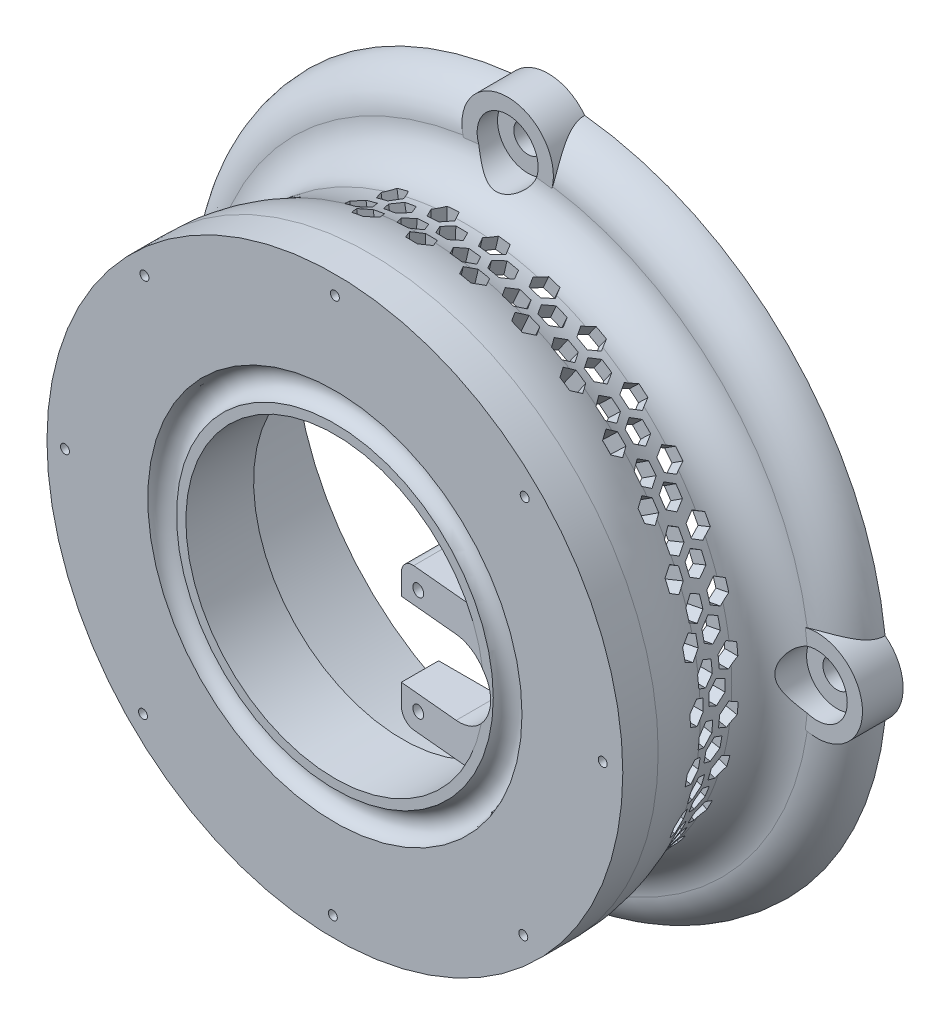
SolidWorks part; units mm, degrees
note: '?' marks a value the reader was unsure of. The reader was unsure of these and kept them because the rebuilt part matched: shared geometry of "Szkic4<2>", "Szkic25<3>".
ref_plane "Płaszczyzna przednia" through (0, 0, 0) normal (0, 0, 1) x (1, 0, 0)
ref_plane "Płaszczyzna górna" through (0, 0, 0) normal (0, 1, 0) x (1, 0, 0)
ref_plane "Płaszczyzna prawa" through (0, 0, 0) normal (1, 0, 0) x (0, 0, -1)
ref_plane "Płaszczyzna4" through (0, 0, -2) normal (0, 0, -1) x (-1, 0, 0)
sketch "Szkic2" plane through (0, 0, -2) normal (0, 0, 1) x (1, 0, 0)
  line L0 (68.9829, 1.0093) -> (-61.0171, 1.0093) construction
  circle A0 centre (3.9829, 1.0093) radius 44
  circle A1 centre (3.9829, 1.0093) radius 85
  circle A10 centre (3.9829, 1.0093) radius 65 construction
  dimension "D1" = 170
  dimension "D2" = 88
extrude "Dodanie-wyciągnięcie1" add sketch "Szkic2" against normal blind 20
ref_axis "Oś1" through (3.9829, 1.0093, -22) along (0, 0, 1)?
sketch "Szkic4" plane through (3.9829, 0, -274.858) normal (1, 0, 0) x (0, 0, -1)
  line L0 (-272.858, -79.75) -> (-272.858, 79.75) construction
  line L1 (-272.858, 56.2487) -> (-272.858, 47.7699)
  line L2 (-252.858, 1.0093) -> (-213.5294, 1.0093) construction
  line L3 (-252.858, -83.9907) -> (-252.858, 86.0093) construction
  circle A0 centre (-273.158, 52.0093) radius 4.25 construction
  arc A1 (-274.858, 55.9045) -> (-277.408, 52.0093) centre (-273.158, 52.0093) ccw construction
  arc A2 (-272.858, 56.2487) -> (-272.858, 47.7699) centre (-273.158, 52.0093) cw
revolve "Wycięcie-obrót3" cut sketch "Szkic4" angle 360 about L2
fillet "Zaokrąglenie1" [suppressed] radius 1
sketch "Szkic7" plane through (0, 0, -22) normal (0, 0, -1) x (-1, 0, 0)
  line L2 (-25, 21.5) -> (-58.093, 21.5)
  line L3 (-59.1555, -21.5) -> (-25, -21.5)
  line L4 (-58.093, 21.5) -> (-63.1555, 17)
  line L5 (-63.1555, 17) -> (-63.1555, -17)
  line L6 (-63.1555, -17) -> (-59.1555, -21.5)
  line L7 (-25, 21.5) -> (-25, -21.5)
  line L8 (0, 0) -> (-103.1393, 0) construction
  dimension "D1" = 43
  dimension "D2" = 25
extrude "Wytnij-wyciągnięcie1" cut sketch "Szkic7" against normal up to surface (6.55 mm away)
sketch "Szkic8" plane through (0, 0, 0) normal (0, 1, 0) x (1, 0, 0)
  line L0 (21.1555, 15.45) -> (21.1555, 4.45)
  line L1 (79.75, 2) -> (-79.75, 2) construction
  line L2 (-81.0171, 2) -> (88.9829, 2) construction
  line L3 (47.9713, 2) -> (47.9713, 15.45)
  line L5 (47.9713, 15.45) -> (21.1555, 15.45)
  line L6 (21.1555, 4.45) -> (47.9713, 2)
  line L8 (-40.0171, 2) -> (47.9829, 2) construction
  line L9 (42.9204, 15.45) -> (58.093, 15.45) construction
  dimension "D1" = 11
extrude "Dodanie-wyciągnięcie2" add sketch "Szkic8" along normal up to vertex and the other way up to vertex
revolve "Wycięcie-obrót4" cut sketch "Szkic4<2>" angle 360 about L2
sketch "Szkic4<2>" plane through (3.9829, 0, -274.858) normal (1, 0, 0) x (0, 0, -1) same geometry as "Szkic4"
fillet "Zaokrąglenie2" radius 4 2 edges at (21.1555, -21, -9.95) (21.1555, 21, -9.95)
sketch "Szkic11" plane through (0, 0, -22) normal (0, 0, -1) x (-1, 0, 0)
  circle A0 centre (-26.6555, 15.5) radius 1.75
  circle A3 centre (-26.6555, -15.5) radius 1.75
  dimension "D2" = 3.5
extrude "Wytnij-wyciągnięcie3" cut sketch "Szkic11" against normal through all
ref_axis "Oś2" through (3.9829, 1.0093, -22) along (0, 0, 1)?
ref_plane "Płaszczyzna5" through (3.9829, 0, 0) normal (1, 0, 0) x (0, 0, -1)
sketch "Szkic12" plane through (0, 0, -15.45) normal (0, 0, -1) x (-1, 0, 0)
  line L0 (-21.1555, 0) -> (-93.814, 0) construction
  line L1 (-21.1555, 17) -> (-21.1555, -17) construction
  line L2 (-21.1555, 11) -> (-38.9713, 11)
  line L3 (-21.1555, -11) -> (-38.9713, -11)
  line L4 (-21.1555, 11) -> (-21.1555, -11)
  arc A0 (-38.9713, 11) -> (-38.9713, -11) centre (-38.9713, 0) ccw
  dimension "D1" = 11
extrude "Wytnij-wyciągnięcie5" cut sketch "Szkic12" against normal through all
sketch "Szkic14" plane through (3.9829, 0, 0) normal (1, 0, 0) x (0, -1, 0)
  line L0 (-86.0093, 65) -> (-101.0093, 65)
  line L3 (-76.0093, 65) -> (-76.0093, 22)
  line L4 (83.9907, 22) -> (-86.0093, 22) construction
  line L5 (-76.0093, 22) -> (-86.0093, 22)
  line L6 (-86.0093, 65) -> (-76.0093, 65)
  line L8 (-1.0093, 22) -> (-1.0093, 150.2806) construction
  arc A0 (-86.0093, 22) -> (-86.0093, 65) centre (-119.7398, 43.5) ccw construction
  arc A1 (-101.0093, 65) -> (-90.3789, 53.0784) centre (-89.0093, 65) ccw
  arc A2 (-90.3789, 53.0784) -> (-79.8685, 40.294) centre (-91.738, 41.2484) cw
  arc A3 (-79.8685, 40.294) -> (-86.0093, 22) centre (-119.7398, 43.5) cw
  point P1 (-91.1471, 45.0003)
  point P16 (-84.5062, 36.6826)
  point P17 (-84.4983, 37.0312)
  point P18 (-84.0434, 37.643)
  point P19 (0, 0)
  point P20 (-79.8685, 40.294)
  dimension "D3" = 40
  dimension "D4" = 12
  dimension "D1" = 10
  dimension "D2" = 43
  dimension "D5" = 15
revolve "Obrót2" add sketch "Szkic14" angle 360 about L8
sketch "Szkic15" plane through (0, 0, -2) normal (0, 0, 1) x (1, 0, 0)
  line L0 (3.9829, 1.0093) -> (99.0167, 1.0093) construction
  circle A0 centre (3.9829, 80.5093) radius 1.325
  circle A1 centre (60.0211, 57.0475) radius 1.325
  circle A2 centre (83.0561, 0.8325) radius 1.325
  circle A3 centre (59.5943, -55.2057) radius 1.325
  circle A4 centre (3.3793, -78.2407) radius 1.325
  circle A5 centre (-52.6589, -54.7789) radius 1.325
  circle A6 centre (-75.6939, 1.436) radius 1.325
  circle A7 centre (-52.2321, 57.4743) radius 1.325
  point P23 (3.6811, 1.1343)
  dimension "D1" = 2.65
extrude "Wytnij-wyciągnięcie6" cut sketch "Szkic15" against normal blind 10
sketch "Szkic16" plane through (3.9829, 0, 0) normal (1, 0, 0) x (0, 0, -1)
  line L0 (0, 0) -> (122.0759, 0) construction
  line L1 (29, 38) -> (58, 38)
  line L2 (29, 38) -> (29, -38)
  line L3 (29, -38) -> (58, -38)
  line L4 (58, 38) -> (58, -38)
  line L7 (65, -73.9907) -> (65, 76.0093) construction
  line L8 (22, 86.0093) -> (22, -83.9907) construction
  dimension "D1" = 76
  dimension "D2" = 29
  dimension "D3" = 7
  dimension "D4" = 7
extrude "Wytnij-wyciągnięcie7" [suppressed] cut sketch "Szkic16" against normal through all
sketch "Szkic17" plane through (0, 0, -65) normal (0, 0, -1) x (-1, 0, 0)
  circle A8 centre (-3.9829, 80.2593) radius 1.325
  circle A9 centre (52.0553, 57.0475) radius 1.325
  circle A11 centre (52.0553, -55.0289) radius 1.325
  circle A12 centre (-3.9829, -78.2407) radius 1.325
  circle A13 centre (-60.0211, -55.0289) radius 1.325
  circle A14 centre (-83.2329, 1.0093) radius 1.325
  circle A15 centre (-60.0211, 57.0475) radius 1.325
  dimension "D1" = 2.65
extrude "Wytnij-wyciągnięcie8" [suppressed] cut sketch "Szkic17" against normal blind 20
fillet "Zaokrąglenie3" [suppressed] radius 13
ref_plane "Płaszczyzna6" through (88.9829, 0, 0) normal (1, 0, 0) x (0, 0, -1)
sketch "Szkic18" plane through (88.9829, 0, 0) normal (1, 0, 0) x (0, 0, -1)
  line L0 (65, 1.0093) -> (-68.0601, 1.0093) construction
  line L2 (82.2414, 1.0093) -> (79.2132, 7.04)
  line L3 (79.2132, 7.04) -> (72.0202, 9.3115)
  line L4 (72.0202, 9.3115) -> (70.6324, 9.3115)
  line L5 (70.6324, 9.3115) -> (59.9482, 15.6608)
  line L6 (59.9482, 15.6608) -> (56.2775, 16.8199)
  line L7 (56.2775, 16.8199) -> (48.7074, 15.4124)
  line L8 (48.7074, 15.4124) -> (33.0479, 17.6738)
  line L9 (33.0479, 17.6738) -> (40.7014, 6.3855)
  line L10 (40.7014, 6.3855) -> (39.8206, 4.503)
  line L11 (39.8206, 4.503) -> (39.8206, -2.4844)
  line L12 (40.7014, -4.367) -> (39.8206, -2.4844)
  line L13 (33.0479, -15.6553) -> (40.7014, -4.367)
  line L14 (48.7074, -13.3938) -> (33.0479, -15.6553)
  line L15 (56.2775, -14.8014) -> (48.7074, -13.3938)
  line L16 (59.9482, -13.6422) -> (56.2775, -14.8014)
  line L17 (70.6324, -7.293) -> (59.9482, -13.6422)
  line L18 (72.0202, -7.293) -> (70.6324, -7.293)
  line L19 (79.2132, -5.0215) -> (72.0202, -7.293)
  line L20 (82.2414, 1.0093) -> (79.2132, -5.0215)
  line L21 (78.8845, 1.0093) -> (77.101, 4.561)
  line L22 (77.101, 4.561) -> (71.5578, 6.3115)
  line L23 (71.5578, 6.3115) -> (69.8083, 6.3115)
  line L24 (69.8083, 6.3115) -> (58.7139, 12.9045)
  line L25 (58.7139, 12.9045) -> (56.0889, 13.7335)
  line L26 (56.0889, 13.7335) -> (48.7688, 12.3724)
  line L27 (48.7688, 12.3724) -> (39.344, 13.7335)
  line L28 (39.344, 13.7335) -> (44.1411, 6.6582)
  line L29 (44.1411, 6.6582) -> (42.8206, 3.8359)
  line L30 (42.8206, 3.8359) -> (42.8206, -1.8173)
  line L31 (44.1411, -4.6396) -> (42.8206, -1.8173)
  line L32 (39.344, -11.7149) -> (44.1411, -4.6396)
  line L33 (48.7688, -10.3538) -> (39.344, -11.7149)
  line L34 (56.0889, -11.7149) -> (48.7688, -10.3538)
  line L35 (58.7139, -10.886) -> (56.0889, -11.7149)
  line L36 (69.8083, -4.293) -> (58.7139, -10.886)
  line L37 (71.5578, -4.293) -> (69.8083, -4.293)
  line L38 (77.101, -2.5424) -> (71.5578, -4.293)
  line L39 (78.8845, 1.0093) -> (77.101, -2.5424)
  line L40 (65, -1.9907) -> (-68.0601, -1.9907)
  line L41 (65, -98.9907) -> (65, 101.0093) construction
  point P16 (39.8206, 1.0093)
  dimension "D1" = 3
extrude "Wytnij-wyciągnięcie9" [suppressed] cut sketch "Szkic18" against normal blind 6 contours L0 L2 L3 L4 L5 L6 L7 L8 L9 L10 L11 L30 L29 L28 L27 L26 L25 L24 L23 L22 L21 | L20 L40 L39 L38 L37 L36 L35 L34 L33 L32 L31 L30 L11 L12 L13 L14 L15 L16 L17 L18 L19 | L20 L0 L39 L40 | L30 L0 L11 L40
sketch "Szkic19" [suppressed] plane through (0, 0, -22) normal (0, 0, -1) x (-1, 0, 0)
  line L0 (-40.0802, 26.1683) -> (-65.9424, 43.2705)
  line L1 (-83.2329, 1.0093) -> (99.2698, 1.0093) construction
  line L2 (-40.0802, -24.1498) -> (-65.9424, -41.252)
  arc A0 (-41.7894, -21.5) -> (-42.9204, 21.5) centre (-3.9829, 1.0093) ccw construction
  arc A1 (-65.9424, 43.2705) -> (-65.9424, -41.252) centre (-3.9829, 1.0093) cw
  arc A3 (-40.0802, 26.1683) -> (-40.0802, -24.1498) centre (-3.9829, 1.0093) cw
  circle A4 centre (-3.9829, 1.0093) radius 75 construction
extrude "Wytnij-wyciągnięcie10" [suppressed] cut sketch "Szkic19" against normal blind 12
fillet "Zaokrąglenie4" [suppressed] radius 2
sketch "Szkic20" plane through (0, 0, 0) normal (1, 0, 0) x (0, 0, -1)
  line L0 (0, 0) -> (109, 0) construction
  line L1 (39.0718, 14.9113) -> (42.5359, 16.9113)
  line L2 (42.5359, 16.9113) -> (45.9536, 14.9381)
  line L3 (42.5359, 12.9649) -> (45.9536, 14.9381)
  line L4 (39.0718, 14.9113) -> (42.5359, 12.9649)
  line L5 (50.5359, 16.9113) -> (53.9536, 14.9381)
  line L7 (50.5359, 12.9649) -> (53.9536, 14.9381)
  line L8 (47.0718, 14.9113) -> (50.5359, 16.9113)
  line L9 (47.0718, 14.9113) -> (50.5359, 12.9649)
  line L10 (58.5359, 16.9113) -> (61.9536, 14.9381)
  line L11 (58.5359, 12.9649) -> (61.9536, 14.9381)
  line L12 (55.0718, 14.9113) -> (58.5359, 16.9113)
  line L13 (55.0718, 14.9113) -> (58.5359, 12.9649)
  line L14 (55.0718, -14.9113) -> (58.5359, -12.9649)
  line L15 (55.0718, -14.9113) -> (58.5359, -16.9113)
  line L16 (58.5359, -12.9649) -> (61.9536, -14.9381)
  line L17 (58.5359, -16.9113) -> (61.9536, -14.9381)
  line L18 (47.0718, -14.9113) -> (50.5359, -12.9649)
  line L19 (47.0718, -14.9113) -> (50.5359, -16.9113)
  line L20 (50.5359, -12.9649) -> (53.9536, -14.9381)
  line L21 (50.5359, -16.9113) -> (53.9536, -14.9381)
  line L22 (39.0718, -14.9113) -> (42.5359, -12.9649)
  line L23 (42.5359, -12.9649) -> (45.9536, -14.9381)
  line L24 (42.5359, -16.9113) -> (45.9536, -14.9381)
  line L25 (39.0718, -14.9113) -> (42.5359, -16.9113)
  line L26 (65, -98.9907) -> (65, 101.0093) construction
  line L30 (40, 0) -> (149, 0) construction
  line L31 (31.0718, 5) -> (34.5359, 7)
  line L32 (34.5359, 7) -> (38, 5)
  line L33 (17.5359, 3) -> (38, 5)
  line L34 (31.0718, 5) -> (17.5359, 3)
  line L35 (35.0718, 0) -> (0, 0) construction
  line L36 (17.5359, -15.38) -> (17.5359, 15.38) construction
  line L37 (39.0718, 5) -> (42.5359, 7)
  line L38 (42.5359, 7) -> (46, 5)
  line L39 (25.5359, 3) -> (46, 5)
  line L40 (39.0718, 5) -> (25.5359, 3)
  line L41 (25.5359, -15.38) -> (25.5359, 15.38) construction
  line L42 (47.0718, 5) -> (50.5359, 7)
  line L43 (50.5359, 7) -> (54, 5)
  line L44 (33.5359, 3) -> (54, 5)
  line L45 (47.0718, 5) -> (33.5359, 3)
  line L46 (33.5359, -15.38) -> (33.5359, 15.38) construction
  line L47 (55.0718, 5) -> (58.5359, 7)
  line L48 (58.5359, 7) -> (62, 5)
  line L49 (41.5359, 3) -> (62, 5)
  line L50 (55.0718, 5) -> (41.5359, 3)
  line L51 (41.5359, -15.38) -> (41.5359, 15.38) construction
  line L52 (63.0718, 5) -> (66.5359, 7)
  line L53 (66.5359, 7) -> (70, 5)
  line L54 (49.5359, 3) -> (70, 5)
  line L55 (63.0718, 5) -> (49.5359, 3)
  line L56 (49.5359, -15.38) -> (49.5359, 15.38) construction
  line L57 (30.8787, 17.2091) -> (38.5359, 21.63)
  line L58 (38.5359, 21.63) -> (58.726, 9.9732)
  line L59 (38.5359, 8) -> (58.726, 9.9732)
  line L60 (30.8787, 17.2091) -> (38.5359, 8)
  line L61 (38.8787, 17.2091) -> (46.5359, 21.63)
  line L62 (46.5359, 21.63) -> (66.726, 9.9732)
  line L63 (46.5359, 8) -> (66.726, 9.9732)
  line L64 (38.8787, 17.2091) -> (46.5359, 8)
  line L65 (46.8787, 17.2091) -> (54.5359, 21.63)
  line L66 (54.5359, 21.63) -> (74.726, 9.9732)
  line L67 (54.5359, 8) -> (74.726, 9.9732)
  line L68 (46.8787, 17.2091) -> (54.5359, 8)
  line L69 (54.8787, 17.2091) -> (62.5359, 21.63)
  line L70 (62.5359, 21.63) -> (82.726, 9.9732)
  line L71 (62.5359, 8) -> (82.726, 9.9732)
  line L72 (54.8787, 17.2091) -> (62.5359, 8)
  line L73 (54.8787, -17.2091) -> (62.5359, -8)
  line L74 (62.5359, -8) -> (82.726, -9.9732)
  line L75 (62.5359, -21.63) -> (82.726, -9.9732)
  line L76 (54.8787, -17.2091) -> (62.5359, -21.63)
  line L77 (46.8787, -17.2091) -> (54.5359, -8)
  line L78 (54.5359, -8) -> (74.726, -9.9732)
  line L79 (54.5359, -21.63) -> (74.726, -9.9732)
  line L80 (46.8787, -17.2091) -> (54.5359, -21.63)
  line L81 (38.8787, -17.2091) -> (46.5359, -8)
  line L82 (46.5359, -8) -> (66.726, -9.9732)
  line L83 (46.5359, -21.63) -> (66.726, -9.9732)
  line L84 (38.8787, -17.2091) -> (46.5359, -21.63)
  line L85 (30.8787, -17.2091) -> (38.5359, -8)
  line L86 (38.5359, -8) -> (58.726, -9.9732)
  line L87 (38.5359, -21.63) -> (58.726, -9.9732)
  line L88 (30.8787, -17.2091) -> (38.5359, -21.63)
  line L89 (63.0718, -5) -> (49.5359, -3)
  line L90 (49.5359, -3) -> (70, -5)
  line L91 (66.5359, -7) -> (70, -5)
  line L92 (63.0718, -5) -> (66.5359, -7)
  line L93 (55.0718, -5) -> (41.5359, -3)
  line L94 (41.5359, -3) -> (62, -5)
  line L95 (58.5359, -7) -> (62, -5)
  line L96 (55.0718, -5) -> (58.5359, -7)
  line L97 (47.0718, -5) -> (33.5359, -3)
  line L98 (33.5359, -3) -> (54, -5)
  line L99 (50.5359, -7) -> (54, -5)
  line L100 (47.0718, -5) -> (50.5359, -7)
  line L101 (39.0718, -5) -> (25.5359, -3)
  line L102 (25.5359, -3) -> (46, -5)
  line L103 (42.5359, -7) -> (46, -5)
  line L104 (39.0718, -5) -> (42.5359, -7)
  line L105 (31.0718, -5) -> (17.5359, -3)
  line L106 (17.5359, -3) -> (38, -5)
  line L107 (34.5359, -7) -> (38, -5)
  line L108 (31.0718, -5) -> (34.5359, -7)
  line L109 (67.0718, 0) -> (70.5359, 2)
  line L110 (70.5359, 2) -> (74, 0)
  line L111 (70.5359, -2) -> (74, 0)
  line L112 (67.0718, 0) -> (70.5359, -2)
  line L113 (59.0718, 0) -> (62.5359, 2)
  line L114 (62.5359, 2) -> (66, 0)
  line L115 (62.5359, -2) -> (66, 0)
  line L116 (59.0718, 0) -> (62.5359, -2)
  line L117 (51.0718, 0) -> (54.5359, 2)
  line L118 (54.5359, 2) -> (58, 0)
  line L119 (54.5359, -2) -> (58, 0)
  line L120 (51.0718, 0) -> (54.5359, -2)
  line L121 (43.0718, 0) -> (46.5359, 2)
  line L122 (46.5359, 2) -> (50, 0)
  line L123 (46.5359, -2) -> (50, 0)
  line L124 (43.0718, 0) -> (46.5359, -2)
  line L125 (35.0718, 0) -> (38.5359, 2)
  line L126 (38.5359, 2) -> (42, 0)
  line L127 (38.5359, -2) -> (42, 0)
  line L128 (27.0718, 0) -> (3.9914, 0.2614)
  line L129 (3.9914, 0.2614) -> (0, 0)
  line L130 (3.9914, -0.2614) -> (0, 0)
  line L131 (27.0718, 0) -> (3.9914, -0.2614)
  line L132 (35.0718, 0) -> (38.5359, -2)
  line L133 (32, 0) -> (141, 0) construction
  line L134 (24, 0) -> (133, 0) construction
  line L135 (16, 0) -> (125, 0) construction
  line L136 (8, 0) -> (117, 0) construction
  point P74 (49.5359, 0)
  point P87 (41.5359, 0)
  point P88 (33.5359, 0)
  point P89 (25.5359, 0)
  point P90 (17.5359, 0)
  dimension "D1" = 2.9916
  dimension "D2" = 4
  dimension "D3" = 65
  dimension "D4" = 3
  dimension "D6" = 3
  dimension "D8" = 3
  dimension "D5" = 6
  dimension "D7" = 5
  dimension "D9" = 4
extrude "Wytnij-wyciągnięcie11" [suppressed] cut sketch "Szkic20" along normal through all
sketch "Szkic21" plane through (0, 0, 0) normal (1, 0, 0) x (0, 0, -1)
  line L0 (22, 1.0093) -> (75, 1.0093) construction
  line L3 (40.5, 4.4734) -> (37.5, 2.7413)
  line L4 (48.5, 4.4734) -> (45.5, 2.7413)
  line L5 (45.5, 2.7413) -> (45.5, -0.7228)
  line L6 (45.5, -0.7228) -> (48.5, -2.4548)
  line L7 (48.5, -2.4548) -> (51.5, -0.7228)
  line L8 (51.5, -0.7228) -> (51.5, 2.7413)
  line L9 (51.5, 2.7413) -> (48.5, 4.4734)
  line L10 (37.5, 2.7413) -> (37.5, -0.7228)
  line L11 (37.5, -0.7228) -> (40.5, -2.4548)
  line L12 (40.5, -2.4548) -> (43.5, -0.7228)
  line L13 (43.5, -0.7228) -> (43.5, 2.7413)
  line L14 (43.5, 2.7413) -> (40.5, 4.4734)
  line L15 (14, 1.0093) -> (67, 1.0093) construction
  line L16 (32.5, 4.4734) -> (29.5, 2.7413)
  line L17 (29.5, 2.7413) -> (29.5, -0.7228)
  line L18 (29.5, -0.7228) -> (32.5, -2.4548)
  line L19 (32.5, -2.4548) -> (35.5, -0.7228)
  line L20 (35.5, -0.7228) -> (35.5, 2.7413)
  line L21 (35.5, 2.7413) -> (32.5, 4.4734)
  line L22 (6, 1.0093) -> (59, 1.0093) construction
  line L23 (40.5, 12.4734) -> (37.5, 10.7413)
  line L24 (37.5, 10.7413) -> (37.5, 7.2772)
  line L25 (37.5, 7.2772) -> (40.5, 5.5452)
  line L26 (40.5, 5.5452) -> (43.5, 7.2772)
  line L27 (43.5, 7.2772) -> (43.5, 10.7413)
  line L28 (43.5, 10.7413) -> (40.5, 12.4734)
  line L29 (14, 9.0093) -> (67, 9.0093) construction
  line L30 (32.5, 12.4734) -> (29.5, 10.7413)
  line L31 (29.5, 10.7413) -> (29.5, 7.2772)
  line L32 (29.5, 7.2772) -> (32.5, 5.5452)
  line L33 (32.5, 5.5452) -> (35.5, 7.2772)
  line L34 (35.5, 7.2772) -> (35.5, 10.7413)
  line L35 (35.5, 10.7413) -> (32.5, 12.4734)
  line L36 (6, 9.0093) -> (59, 9.0093) construction
  line L37 (40.5, 20.4734) -> (37.5, 18.7413)
  line L38 (37.5, 18.7413) -> (37.5, 15.2772)
  line L39 (37.5, 15.2772) -> (40.5, 13.5452)
  line L40 (40.5, 13.5452) -> (43.5, 15.2772)
  line L41 (43.5, 15.2772) -> (43.5, 18.7413)
  line L42 (43.5, 18.7413) -> (40.5, 20.4734)
  line L43 (14, 17.0093) -> (67, 17.0093) construction
  line L44 (32.5, 20.4734) -> (29.5, 18.7413)
  line L45 (29.5, 18.7413) -> (29.5, 15.2772)
  line L46 (29.5, 15.2772) -> (32.5, 13.5452)
  line L47 (32.5, 13.5452) -> (35.5, 15.2772)
  line L48 (35.5, 15.2772) -> (35.5, 18.7413)
  line L49 (35.5, 18.7413) -> (32.5, 20.4734)
  line L50 (6, 17.0093) -> (59, 17.0093) construction
  line L51 (40.5, 28.4734) -> (37.5, 26.7413)
  line L52 (37.5, 26.7413) -> (37.5, 23.2772)
  line L53 (37.5, 23.2772) -> (40.5, 21.5452)
  line L54 (40.5, 21.5452) -> (43.5, 23.2772)
  line L55 (43.5, 23.2772) -> (43.5, 26.7413)
  line L56 (43.5, 26.7413) -> (40.5, 28.4734)
  line L57 (14, 25.0093) -> (67, 25.0093) construction
  line L58 (32.5, 28.4734) -> (29.5, 26.7413)
  line L59 (29.5, 26.7413) -> (29.5, 23.2772)
  line L60 (29.5, 23.2772) -> (32.5, 21.5452)
  line L61 (32.5, 21.5452) -> (35.5, 23.2772)
  line L62 (35.5, 23.2772) -> (35.5, 26.7413)
  line L63 (35.5, 26.7413) -> (32.5, 28.4734)
  line L64 (6, 25.0093) -> (59, 25.0093) construction
  line L65 (48.5, 12.4734) -> (45.5, 10.7413)
  line L66 (45.5, 10.7413) -> (45.5, 7.2772)
  line L67 (45.5, 7.2772) -> (48.5, 5.5452)
  line L68 (48.5, 5.5452) -> (51.5, 7.2772)
  line L69 (51.5, 7.2772) -> (51.5, 10.7413)
  line L70 (51.5, 10.7413) -> (48.5, 12.4734)
  line L71 (22, 9.0093) -> (75, 9.0093) construction
  line L72 (48.5, 20.4734) -> (45.5, 18.7413)
  line L73 (45.5, 18.7413) -> (45.5, 15.2772)
  line L74 (45.5, 15.2772) -> (48.5, 13.5452)
  line L75 (48.5, 13.5452) -> (51.5, 15.2772)
  line L76 (51.5, 15.2772) -> (51.5, 18.7413)
  line L77 (51.5, 18.7413) -> (48.5, 20.4734)
  line L78 (22, 17.0093) -> (75, 17.0093) construction
  line L79 (48.5, 28.4734) -> (45.5, 26.7413)
  line L80 (45.5, 26.7413) -> (45.5, 23.2772)
  line L81 (45.5, 23.2772) -> (48.5, 21.5452)
  line L82 (48.5, 21.5452) -> (51.5, 23.2772)
  line L83 (51.5, 23.2772) -> (51.5, 26.7413)
  line L84 (51.5, 26.7413) -> (48.5, 28.4734)
  line L85 (22, 25.0093) -> (75, 25.0093) construction
  line L86 (22, -22.9907) -> (75, -22.9907) construction
  line L87 (22, -14.9907) -> (75, -14.9907) construction
  line L88 (22, -6.9907) -> (75, -6.9907) construction
  line L89 (14, -14.9907) -> (67, -14.9907) construction
  line L90 (6, -6.9907) -> (59, -6.9907) construction
  line L91 (14, -6.9907) -> (67, -6.9907) construction
  line L92 (51.5, -24.7228) -> (48.5, -26.4548)
  line L93 (51.5, -21.2587) -> (51.5, -24.7228)
  line L94 (48.5, -19.5266) -> (51.5, -21.2587)
  line L95 (45.5, -21.2587) -> (48.5, -19.5266)
  line L96 (45.5, -24.7228) -> (45.5, -21.2587)
  line L97 (48.5, -26.4548) -> (45.5, -24.7228)
  line L98 (51.5, -16.7228) -> (48.5, -18.4548)
  line L99 (51.5, -13.2587) -> (51.5, -16.7228)
  line L100 (48.5, -11.5266) -> (51.5, -13.2587)
  line L101 (45.5, -13.2587) -> (48.5, -11.5266)
  line L102 (45.5, -16.7228) -> (45.5, -13.2587)
  line L103 (48.5, -18.4548) -> (45.5, -16.7228)
  line L104 (51.5, -8.7228) -> (48.5, -10.4548)
  line L105 (51.5, -5.2587) -> (51.5, -8.7228)
  line L106 (48.5, -3.5266) -> (51.5, -5.2587)
  line L107 (45.5, -5.2587) -> (48.5, -3.5266)
  line L108 (45.5, -8.7228) -> (45.5, -5.2587)
  line L109 (48.5, -10.4548) -> (45.5, -8.7228)
  line L110 (43.5, -16.7228) -> (40.5, -18.4548)
  line L111 (43.5, -13.2587) -> (43.5, -16.7228)
  line L112 (40.5, -11.5266) -> (43.5, -13.2587)
  line L113 (37.5, -13.2587) -> (40.5, -11.5266)
  line L114 (37.5, -16.7228) -> (37.5, -13.2587)
  line L115 (40.5, -18.4548) -> (37.5, -16.7228)
  line L116 (35.5, -8.7228) -> (32.5, -10.4548)
  line L117 (35.5, -5.2587) -> (35.5, -8.7228)
  line L118 (32.5, -3.5266) -> (35.5, -5.2587)
  line L119 (29.5, -5.2587) -> (32.5, -3.5266)
  line L120 (29.5, -8.7228) -> (29.5, -5.2587)
  line L121 (32.5, -10.4548) -> (29.5, -8.7228)
  line L122 (43.5, -8.7228) -> (40.5, -10.4548)
  line L123 (43.5, -5.2587) -> (43.5, -8.7228)
  line L124 (40.5, -3.5266) -> (43.5, -5.2587)
  line L125 (37.5, -5.2587) -> (40.5, -3.5266)
  line L126 (37.5, -8.7228) -> (37.5, -5.2587)
  line L127 (40.5, -10.4548) -> (37.5, -8.7228)
  line L128 (35.5, -0.7228) -> (32.5, -2.4548)
  line L129 (32.5, 4.4734) -> (35.5, 2.7413)
  line L130 (29.5, 2.7413) -> (32.5, 4.4734)
  line L131 (32.5, -2.4548) -> (29.5, -0.7228)
  line L132 (43.5, -0.7228) -> (40.5, -2.4548)
  line L133 (40.5, 4.4734) -> (43.5, 2.7413)
  line L134 (37.5, 2.7413) -> (40.5, 4.4734)
  line L135 (51.5, -0.7228) -> (48.5, -2.4548)
  line L136 (48.5, 4.4734) -> (51.5, 2.7413)
  line L137 (45.5, 2.7413) -> (48.5, 4.4734)
  line L138 (48.5, -2.4548) -> (45.5, -0.7228)
  line L139 (40.5, -2.4548) -> (37.5, -0.7228)
  line L140 (48.5, 1.0093) -> (48.5, -84.9338) construction
  line L141 (83, -6.9907) -> (30, -6.9907) construction
  line L142 (91, -6.9907) -> (38, -6.9907) construction
  line L143 (83, -14.9907) -> (30, -14.9907) construction
  line L144 (83, 17.0093) -> (30, 17.0093) construction
  line L145 (91, 9.0093) -> (38, 9.0093) construction
  line L146 (83, 9.0093) -> (30, 9.0093) construction
  line L147 (91, 1.0093) -> (38, 1.0093) construction
  line L148 (83, 1.0093) -> (30, 1.0093) construction
  line L149 (56.5, -2.4548) -> (59.5, -0.7228)
  line L150 (48.5, -2.4548) -> (51.5, -0.7228)
  line L151 (51.5, 2.7413) -> (48.5, 4.4734)
  line L152 (48.5, 4.4734) -> (45.5, 2.7413)
  line L153 (45.5, -0.7228) -> (48.5, -2.4548)
  line L154 (59.5, 2.7413) -> (56.5, 4.4734)
  line L155 (56.5, 4.4734) -> (53.5, 2.7413)
  line L156 (53.5, -0.7228) -> (56.5, -2.4548)
  line L157 (64.5, -2.4548) -> (67.5, -0.7228)
  line L158 (67.5, 2.7413) -> (64.5, 4.4734)
  line L159 (64.5, 4.4734) -> (61.5, 2.7413)
  line L160 (61.5, -0.7228) -> (64.5, -2.4548)
  line L161 (56.5, -10.4548) -> (59.5, -8.7228)
  line L162 (59.5, -8.7228) -> (59.5, -5.2587)
  line L163 (59.5, -5.2587) -> (56.5, -3.5266)
  line L164 (56.5, -3.5266) -> (53.5, -5.2587)
  line L165 (53.5, -5.2587) -> (53.5, -8.7228)
  line L166 (53.5, -8.7228) -> (56.5, -10.4548)
  line L167 (64.5, -10.4548) -> (67.5, -8.7228)
  line L168 (67.5, -8.7228) -> (67.5, -5.2587)
  line L169 (67.5, -5.2587) -> (64.5, -3.5266)
  line L170 (64.5, -3.5266) -> (61.5, -5.2587)
  line L171 (61.5, -5.2587) -> (61.5, -8.7228)
  line L172 (61.5, -8.7228) -> (64.5, -10.4548)
  line L173 (56.5, -18.4548) -> (59.5, -16.7228)
  line L174 (59.5, -16.7228) -> (59.5, -13.2587)
  line L175 (59.5, -13.2587) -> (56.5, -11.5266)
  line L176 (56.5, -11.5266) -> (53.5, -13.2587)
  line L177 (53.5, -13.2587) -> (53.5, -16.7228)
  line L178 (53.5, -16.7228) -> (56.5, -18.4548)
  line L179 (48.5, -10.4548) -> (51.5, -8.7228)
  line L180 (51.5, -8.7228) -> (51.5, -5.2587)
  line L181 (51.5, -5.2587) -> (48.5, -3.5266)
  line L182 (48.5, -3.5266) -> (45.5, -5.2587)
  line L183 (45.5, -5.2587) -> (45.5, -8.7228)
  line L184 (45.5, -8.7228) -> (48.5, -10.4548)
  line L185 (48.5, -18.4548) -> (51.5, -16.7228)
  line L186 (51.5, -16.7228) -> (51.5, -13.2587)
  line L187 (51.5, -13.2587) -> (48.5, -11.5266)
  line L188 (48.5, -11.5266) -> (45.5, -13.2587)
  line L189 (45.5, -13.2587) -> (45.5, -16.7228)
  line L190 (45.5, -16.7228) -> (48.5, -18.4548)
  line L191 (48.5, -26.4548) -> (51.5, -24.7228)
  line L192 (51.5, -24.7228) -> (51.5, -21.2587)
  line L193 (51.5, -21.2587) -> (48.5, -19.5266)
  line L194 (48.5, -19.5266) -> (45.5, -21.2587)
  line L195 (45.5, -21.2587) -> (45.5, -24.7228)
  line L196 (45.5, -24.7228) -> (48.5, -26.4548)
  line L197 (45.5, 26.7413) -> (48.5, 28.4734)
  line L198 (45.5, 23.2772) -> (45.5, 26.7413)
  line L199 (48.5, 21.5452) -> (45.5, 23.2772)
  line L200 (51.5, 23.2772) -> (48.5, 21.5452)
  line L201 (51.5, 26.7413) -> (51.5, 23.2772)
  line L202 (48.5, 28.4734) -> (51.5, 26.7413)
  line L203 (45.5, 18.7413) -> (48.5, 20.4734)
  line L204 (45.5, 15.2772) -> (45.5, 18.7413)
  line L205 (48.5, 13.5452) -> (45.5, 15.2772)
  line L206 (51.5, 15.2772) -> (48.5, 13.5452)
  line L207 (51.5, 18.7413) -> (51.5, 15.2772)
  line L208 (48.5, 20.4734) -> (51.5, 18.7413)
  line L209 (45.5, 10.7413) -> (48.5, 12.4734)
  line L210 (45.5, 7.2772) -> (45.5, 10.7413)
  line L211 (48.5, 5.5452) -> (45.5, 7.2772)
  line L212 (51.5, 7.2772) -> (48.5, 5.5452)
  line L213 (51.5, 10.7413) -> (51.5, 7.2772)
  line L214 (48.5, 12.4734) -> (51.5, 10.7413)
  line L215 (53.5, 18.7413) -> (56.5, 20.4734)
  line L216 (53.5, 15.2772) -> (53.5, 18.7413)
  line L217 (56.5, 13.5452) -> (53.5, 15.2772)
  line L218 (59.5, 15.2772) -> (56.5, 13.5452)
  line L219 (59.5, 18.7413) -> (59.5, 15.2772)
  line L220 (56.5, 20.4734) -> (59.5, 18.7413)
  line L221 (61.5, 10.7413) -> (64.5, 12.4734)
  line L222 (61.5, 7.2772) -> (61.5, 10.7413)
  line L223 (64.5, 5.5452) -> (61.5, 7.2772)
  line L224 (67.5, 7.2772) -> (64.5, 5.5452)
  line L225 (67.5, 10.7413) -> (67.5, 7.2772)
  line L226 (64.5, 12.4734) -> (67.5, 10.7413)
  line L227 (53.5, 10.7413) -> (56.5, 12.4734)
  line L228 (53.5, 7.2772) -> (53.5, 10.7413)
  line L229 (56.5, 5.5452) -> (53.5, 7.2772)
  line L230 (59.5, 7.2772) -> (56.5, 5.5452)
  line L231 (59.5, 10.7413) -> (59.5, 7.2772)
  line L232 (56.5, 12.4734) -> (59.5, 10.7413)
  line L233 (61.5, 2.7413) -> (64.5, 4.4734)
  line L234 (61.5, -0.7228) -> (61.5, 2.7413)
  line L235 (64.5, -2.4548) -> (61.5, -0.7228)
  line L236 (67.5, -0.7228) -> (64.5, -2.4548)
  line L237 (67.5, 2.7413) -> (67.5, -0.7228)
  line L238 (64.5, 4.4734) -> (67.5, 2.7413)
  line L239 (53.5, 2.7413) -> (56.5, 4.4734)
  line L240 (53.5, -0.7228) -> (53.5, 2.7413)
  line L241 (56.5, -2.4548) -> (53.5, -0.7228)
  line L242 (59.5, -0.7228) -> (56.5, -2.4548)
  line L243 (59.5, 2.7413) -> (59.5, -0.7228)
  line L244 (45.5, 2.7413) -> (48.5, 4.4734)
  line L245 (45.5, -0.7228) -> (45.5, 2.7413)
  line L246 (48.5, -2.4548) -> (45.5, -0.7228)
  line L247 (51.5, -0.7228) -> (48.5, -2.4548)
  line L248 (51.5, 2.7413) -> (51.5, -0.7228)
  line L249 (48.5, 4.4734) -> (51.5, 2.7413)
  line L250 (56.5, 4.4734) -> (59.5, 2.7413)
  circle A0 centre (48.5, 1.0093) radius 3 construction
  circle A1 centre (40.5, 1.0093) radius 3 construction
  circle A2 centre (32.5, 1.0093) radius 3 construction
  circle A3 centre (40.5, 9.0093) radius 3 construction
  circle A4 centre (32.5, 9.0093) radius 3 construction
  circle A5 centre (40.5, 17.0093) radius 3 construction
  circle A6 centre (32.5, 17.0093) radius 3 construction
  circle A7 centre (40.5, 25.0093) radius 3 construction
  circle A8 centre (32.5, 25.0093) radius 3 construction
  circle A9 centre (48.5, 9.0093) radius 3 construction
  circle A10 centre (48.5, 17.0093) radius 3 construction
  circle A11 centre (48.5, 25.0093) radius 3 construction
  circle A12 centre (48.5, -22.9907) radius 3 construction
  circle A13 centre (48.5, -14.9907) radius 3 construction
  circle A14 centre (48.5, -6.9907) radius 3 construction
  circle A15 centre (40.5, -14.9907) radius 3 construction
  circle A16 centre (32.5, -6.9907) radius 3 construction
  circle A17 centre (40.5, -6.9907) radius 3 construction
  circle A18 centre (56.5, -6.9907) radius 3 construction
  circle A19 centre (64.5, -6.9907) radius 3 construction
  circle A20 centre (56.5, -14.9907) radius 3 construction
  circle A21 centre (56.5, 17.0093) radius 3 construction
  circle A22 centre (64.5, 9.0093) radius 3 construction
  circle A23 centre (56.5, 9.0093) radius 3 construction
  circle A24 centre (64.5, 1.0093) radius 3 construction
  circle A25 centre (56.5, 1.0093) radius 3 construction
  dimension "D1" = 6
  dimension "D2" = 3
  dimension "D3" = 4
extrude "Wytnij-wyciągnięcie13" [suppressed] cut sketch "Szkic21" along normal through all contours L34 L35 L30 L31 L32 L33 | L20 L21 L16 L17 L18 L19 | L121 L116 L117 L118 L119 L120 | L41 L42 L37 L38 L39 L40 | L27 L28 L23 L24 L25 L26 | L13 L14 L3 L10 L11 L12 | L127 L122 L123 L124 L125 L126 | L115 L110 L111 L112 L113 L114 | L83 L84 L79 L80 L81 L82 | L76 L77 L72 L73 L74 L75 | L69 L70 L65 L66 L67 L68 | L8 L9 L4 L5 L6 L7 | L109 L104 L105 L106 L107 L108 | L103 L98 L99 L100 L101 L102 | L97 L92 L93 L94 L95 L96 | L220 L215 L216 L217 L218 L219 | L232 L227 L228 L229 L230 L231 | L243 L154 L155 L240 L156 L149 | L165 L166 L161 L162 L163 L164 | L177 L178 L173 L174 L175 L176 | L226 L221 L222 L223 L224 L225 | L237 L158 L159 L234 L160 L157 | L171 L172 L167 L168 L169 L170
sketch "Szkic22" plane through (0, 0, 0) normal (1, 0, 0) x (0, 0, -1)
  line L0 (39.3554, -34.3052) -> (39.3554, 52.6948) construction
  line L3 (32.0591, 4.1198) -> (32.0591, 0.6557)
  line L4 (36.3554, 10.9269) -> (36.3554, 7.4628)
  line L5 (36.3554, 7.4628) -> (39.3554, 5.7307)
  line L6 (39.3554, 5.7307) -> (42.3554, 7.4628)
  line L7 (42.3554, 7.4628) -> (42.3554, 10.9269)
  line L8 (42.3554, 10.9269) -> (39.3554, 12.6589)
  line L9 (39.3554, 12.6589) -> (36.3554, 10.9269)
  line L10 (32.0591, 0.6557) -> (35.0591, -1.0763)
  line L11 (35.0591, -1.0763) -> (38.0591, 0.6557)
  line L12 (38.0591, 0.6557) -> (38.0591, 4.1198)
  line L13 (38.0591, 4.1198) -> (35.0591, 5.8519)
  line L14 (35.0591, 5.8519) -> (32.0591, 4.1198)
  line L15 (35.0591, -41.1122) -> (35.0591, 45.8878) construction
  line L22 (30.7627, -47.9192) -> (30.7627, 39.0808) construction
  line L29 (26.4664, -54.7263) -> (26.4664, 32.2737) construction
  line L42 (27.7627, 11.3128) -> (27.7627, 7.8487)
  line L43 (27.7627, 7.8487) -> (30.7627, 6.1167)
  line L44 (30.7627, 6.1167) -> (33.7627, 7.8487)
  line L45 (33.7627, 7.8487) -> (33.7627, 11.3128)
  line L46 (33.7627, 11.3128) -> (30.7627, 13.0449)
  line L47 (30.7627, 13.0449) -> (27.7627, 11.3128)
  line L48 (23.4664, 4.5058) -> (23.4664, 1.0417)
  line L49 (23.4664, 1.0417) -> (26.4664, -0.6904)
  line L50 (26.4664, -0.6904) -> (29.4664, 1.0417)
  line L51 (29.4664, 1.0417) -> (29.4664, 4.5058)
  line L52 (29.4664, 4.5058) -> (26.4664, 6.2378)
  line L53 (26.4664, 6.2378) -> (23.4664, 4.5058)
  line L54 (39.3554, -20.3052) -> (39.3554, 66.6948) construction
  line L55 (35.0591, -27.1122) -> (35.0591, 59.8878) construction
  line L56 (30.7627, -33.9192) -> (30.7627, 53.0808) construction
  line L57 (26.4664, -40.7263) -> (26.4664, 46.2737) construction
  line L82 (39.3554, -6.3052) -> (39.3554, 80.6948) construction
  line L83 (35.0591, -13.1122) -> (35.0591, 73.8878) construction
  line L84 (30.7627, -19.9192) -> (30.7627, 67.0808) construction
  line L85 (26.4664, -26.7263) -> (26.4664, 60.2737) construction
  line L86 (42.3554, 35.4628) -> (42.3554, 38.9269) [skipped]
  line L87 (88.3331, 12.3817) -> (86.8331, 13.2477) [skipped]
  line L88 (36.3554, -2.2406) -> (36.3554, -3.9727) [skipped]
  line L89 (48.5829, 45.9864) -> (47.0829, 45.1204) [skipped]
  line L90 (80.1369, 10.1855) -> (81.6369, 9.3195) [skipped]
  line L91 (46.3867, 37.7903) -> (47.8867, 38.6563) [skipped]
  line L92 (47.2114, 40.8681) -> (45.7114, 40.002) [skipped]
  line L93 (77.3458, 9.4376) -> (74.3458, 11.1697) [skipped]
  line L94 (32.0591, 32.1198) -> (32.0591, 28.6557) [skipped]
  line L95 (69.1496, 7.2415) -> (70.6496, 6.3755) [skipped]
  line L96 (45.0153, 32.6719) -> (46.5153, 33.5379) [skipped]
  line L97 (38.0591, -3.9443) -> (38.0591, 0.0927) [skipped]
  line L98 (36.3554, 24.9269) -> (36.3554, 21.4628) [skipped]
  line L99 (36.3554, 21.4628) -> (39.3554, 19.7307) [skipped]
  line L100 (39.3554, 19.7307) -> (42.3554, 21.4628) [skipped]
  line L101 (42.3554, 21.4628) -> (42.3554, 24.9269) [skipped]
  line L102 (42.3554, 24.9269) -> (39.3554, 26.6589) [skipped]
  line L103 (39.3554, 26.6589) -> (36.3554, 24.9269) [skipped]
  line L110 (38.0591, 18.1198) -> (35.0591, 19.8519) [skipped]
  line L111 (38.0591, 14.6557) -> (38.0591, 18.1198) [skipped]
  line L112 (35.0591, 19.8519) -> (32.0591, 18.1198) [skipped]
  line L113 (32.0591, 18.1198) -> (32.0591, 14.6557) [skipped]
  line L114 (32.0591, 14.6557) -> (35.0591, 12.9237) [skipped]
  line L115 (35.0591, 12.9237) -> (38.0591, 14.6557) [skipped]
  line L122 (23.4664, -9.4942) -> (23.4664, -12.9583) [skipped]
  line L123 (23.4664, -12.9583) -> (26.4664, -14.6904) [skipped]
  line L124 (26.4664, -14.6904) -> (29.4664, -12.9583) [skipped]
  line L125 (29.4664, -12.9583) -> (29.4664, -9.4942) [skipped]
  line L126 (29.4664, -9.4942) -> (26.4664, -7.7622) [skipped]
  line L127 (26.4664, -7.7622) -> (23.4664, -9.4942) [skipped]
  line L128 (27.7627, -2.6872) -> (27.7627, -6.1513) [skipped]
  line L129 (27.7627, -6.1513) -> (30.7627, -7.8833) [skipped]
  line L130 (30.7627, -7.8833) -> (33.7627, -6.1513) [skipped]
  line L131 (33.7627, -6.1513) -> (33.7627, -2.6872) [skipped]
  line L132 (33.7627, -2.6872) -> (30.7627, -0.9551) [skipped]
  line L133 (30.7627, -0.9551) -> (27.7627, -2.6872) [skipped]
  circle A0 centre (39.3554, 9.1948) radius 3 construction
  circle A1 centre (35.0591, 2.3878) radius 3 construction
  circle A6 centre (30.7627, 9.5808) radius 3 construction
  circle A7 centre (26.4664, 2.7737) radius 3 construction
  arc A12 (41.8293, 38.8918) -> (42.1345, 38.3248) centre (39.3554, 37.1948) ccw construction
  arc A13 (37.533, 32.0848) -> (37.831, 31.5351) centre (35.0591, 30.3878) ccw construction
  circle A14 centre (39.3554, 23.1948) radius 3 construction
  circle A16 centre (35.0591, 16.3878) radius 3 construction
  circle A18 centre (26.4664, -11.2263) radius 3 construction
  circle A19 centre (30.7627, -4.4192) radius 3 construction
  dimension "D1" = 6
  dimension "D2" = 4
  dimension "D3" = 3
extrude "Wytnij-wyciągnięcie14" cut sketch "Szkic22" along normal through all
pattern_circular "Szyk kołowy1" count 10 every 11 about axis through (3.9829, 1.0093, 0) along (0, 0, 1) of "Wytnij-wyciągnięcie14"
pattern_circular "Szyk kołowy2" count 10 every 11 about axis through (3.9829, 1.0093, 0) along (0, 0, 1) of "Wytnij-wyciągnięcie14"
sketch "Szkic24" plane through (0, 0, -65) normal (0, 0, -1) x (-1, 0, 0)
  arc A0 (-41.7894, -21.5) -> (-42.9204, 21.5) centre (-3.9829, 1.0093) ccw construction
  line B0 (136.0171, -133.9907) -> (136.0171, 136.0093)
  line B1 (131.0171, 141.0093) -> (-138.9829, 141.0093)
  circle B2 centre (87.2671, 1.0093) radius 3.5
  circle B3 centre (-3.9829, 92.2593) radius 3.5
  line B4 (-33.9829, 96.0093) -> (-33.9829, 41.0093)
  circle B5 centre (-95.2329, 1.0093) radius 3.5
  circle B6 centre (-3.9829, -90.2407) radius 3.5
  line B7 (-108.9829, 41.0093) -> (-108.9829, 96.0093)
  line B8 (-143.9829, 136.0093) -> (-143.9829, -133.9907)
  circle B9 centre (-3.9829, 1.0093) radius 40
sketch_block_instance "SufitStolika-1"
sketch_block "SufitStolika"
sketch "Szkic25" plane through (0, 0, -65) normal (0, 0, -1) x (-1, 0, 0)
  circle A0 centre (-3.9829, -90.2407) radius 3.5 construction
  circle A1 centre (-95.2329, 1.0093) radius 3.5 construction
  circle A2 centre (-3.9829, 92.2593) radius 3.5 construction
  circle A3 centre (87.2671, 1.0093) radius 3.5 construction
  circle A4 centre (-3.9829, -90.2407) radius 3.5
  circle A5 centre (-95.2329, 1.0093) radius 3.5
  circle A6 centre (-3.9829, 92.2593) radius 3.5
  circle A7 centre (87.2671, 1.0093) radius 3.5
  circle A8 centre (-3.9829, -90.2407) radius 13.5
  circle A9 centre (-95.2329, 1.0093) radius 13.5
  circle A10 centre (-3.9829, 92.2593) radius 13.5
  circle A11 centre (87.2671, 1.0093) radius 13.5
  dimension "D1" = 10
extrude "Dodanie-wyciągnięcie3" add sketch "Szkic25<3>" against normal blind 12 contours A8 | A9 | A10 | A11
sketch "Szkic25<3>" plane through (0, 0, -65) normal (0, 0, -1) x (-1, 0, 0) same geometry as "Szkic25"
extrude "Wytnij-wyciągnięcie15" [suppressed] cut sketch "Szkic25" against normal up to next contours A4 | A7 | A6 | A5
hole_wizard "Pogłębienie walcowe pod M8 wkręt do części metalowych z łbem stożkowym ściętym1" positions "Szkic26" profile "Szkic27" counterbore size "M8" standard "Ansi Metric"
sketch "Szkic26" plane through (0, 0, -53) normal (0, 0, 1) x (1, 0, 0)
  point P0 (3.9829, -90.2407)
  point P4 (95.2329, 1.0093)
  point P7 (-87.2671, 1.0093)
  point P10 (3.9829, 92.2593)
sketch "Szkic27" plane through (3.9829, -90.2407, -53) normal (1, 0, 0) x (0, -1, 0)
  line L0 (0, 0) -> (0, 12)
  line L1 (0, 12) -> (4.2, 12)
  line L3 (4.2, 12) -> (4.2, 6)
  line L4 (4.2, 6) -> (9, 6)
  line L5 (9, 6) -> (9, 0)
  line L7 (9, 0) -> (0, 0)
  line L11 (0, -6.35) -> (0, 107.95) construction
  dimension "Średnica otworu na wylot" = 8.4
  dimension "Głębokość otworu na wylot" = 12
  dimension "Średnica pogłębienia walcowego" = 18
  dimension "Głębokość pogłębienia walcowego" = 6
sketch "Szkic28" plane through (0, 0, -59) normal (0, 0, 1) x (1, 0, 0)
  circle A0 centre (-87.2671, 1.0093) radius 9 construction
  circle A1 centre (-87.2671, 1.0093) radius 9
  circle A2 centre (3.9829, -90.2407) radius 9 construction
  circle A3 centre (3.9829, -90.2407) radius 9
  circle A4 centre (3.9829, 92.2593) radius 9 construction
  circle A5 centre (3.9829, 92.2593) radius 9
  circle A6 centre (95.2329, 1.0093) radius 9 construction
  circle A7 centre (95.2329, 1.0093) radius 9
extrude "Wytnij-wyciągnięcie16" cut sketch "Szkic28" along normal up to next
fillet "Zaokrąglenie9" radius 40 1 edges at (88.9829, 1.0093, -22)
